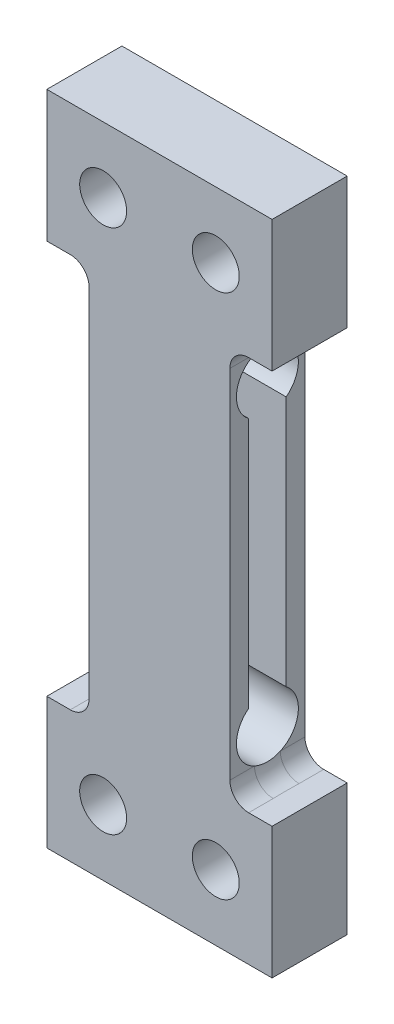
SolidWorks part; units mm, degrees
ref_plane "Front Plane" through (0, 0, 0) normal (0, 0, 1) x (1, 0, 0)
ref_plane "Top Plane" through (0, 0, 0) normal (0, 1, 0) x (1, 0, 0)
ref_plane "Right Plane" through (0, 0, 0) normal (1, 0, 0) x (0, 0, -1)
sketch "Sketch1" plane through (0, 0, 0) normal (0, 0, 1) x (1, 0, 0)
  line L0 (0, 0) -> (-3.75, 0)
  line L1 (-3.75, 0) -> (-3.75, -10.5)
  line L2 (-3.75, -10.5) -> (-6, -10.5)
  line L3 (-6, -10.5) -> (-6, -17.5)
  line L4 (-6, -17.5) -> (0, -17.5)
  line L5 (0, -17.5) -> (0, 0)
  circle A0 centre (-3, -14) radius 1.25
  dimension "D5" = 14
  dimension "D1" = 6
  dimension "D2" = 17.5
  dimension "D3" = 7
  dimension "D4" = 3.75
  dimension "D6" = 3
extrude "Boss-Extrude1" add sketch "Sketch1" along normal blind 4
sketch "Sketch2" plane through (-3.75, 0, 0) normal (-1, 0, 0) x (0, 0, 1)
  line L0 (0, 0) -> (0, -10.5) construction
  line L1 (4, -10.5) -> (0, -10.5) construction
  circle A0 centre (2, -8) radius 1.65
  dimension "D1" = 2
  dimension "D2" = 2.5
extrude "Boss-Extrude2" add sketch "Sketch2" against normal through all
extrude "Cut-Extrude1" cut sketch "Sketch2<2>" against normal through all
sketch "Sketch2<2>" plane through (-3.75, 0, 0) normal (-1, 0, 0) x (0, 0, 1) same geometry as "Sketch2"
mirror "Mirror6" about plane through (0, -17.5, 4) normal (-1, 0, 0) of "Cut-Extrude1", "Boss-Extrude2", "Boss-Extrude1"
mirror "Mirror19" about plane through (0, 0, 0) normal (0, 1, 0) of "Boss-Extrude1", "Mirror6"
sketch "Sketch4" plane through (-3.75, 0, 0) normal (-1, 0, 0) x (0, 0, 1)
  line L0 (0, 10.5) -> (0, -10.5) construction
  line L1 (1, 7.3599) -> (3, 7.3599)
  line L2 (1, 7.3599) -> (1, -8.0133)
  line L3 (1, -8.0133) -> (3, -8.0133)
  line L4 (3, 7.3599) -> (3, -8.0133)
  dimension "D1" = 2
  dimension "D2" = 1
extrude "Cut-Extrude3" cut sketch "Sketch4" against normal through all
fillet "Fillet1" radius 1 4 edges at (3.75, -10.5, 2) (-3.75, -10.5, 2) (-3.75, 10.5, 2) (3.75, 10.5, 2)
